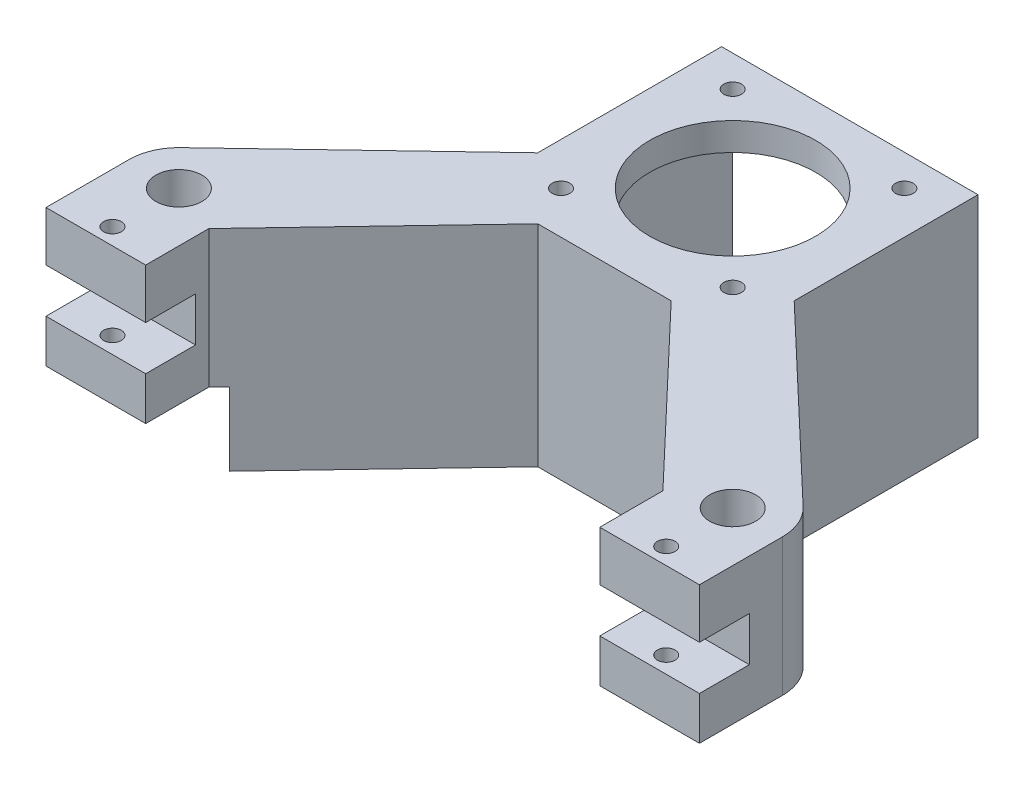
SolidWorks part; units mm, degrees
note: The reader was unsure of these and kept them because the rebuilt part matched: shared geometry of "草图7<7>", "草图7<8>".
ref_plane "前视基准面" through (0, 0, 0) normal (0, 0, 1) x (1, 0, 0)
ref_plane "上视基准面" through (0, 0, 0) normal (0, 1, 0) x (1, 0, 0)
ref_plane "右视基准面" through (0, 0, 0) normal (1, 0, 0) x (0, 0, -1)
sketch "草图6" plane through (0, 0, 0) normal (0, 1, 0) x (1, 0, 0)
  line L1 (-21.15, -21.15) -> (21.15, -21.15)
  line L2 (-21.15, -21.15) -> (-21.15, 21.15)
  line L3 (-21.15, 21.15) -> (21.15, 21.15)
  line L5 (0, 21.15) -> (0, -21.15) construction
  line L6 (-21.15, 0) -> (21.15, 0) construction
  line L8 (21.15, 21.15) -> (21.15, -21.15)
  circle A0 centre (15.5, 15.5) radius 1.6
  circle A1 centre (-15.5, 15.5) radius 1.6
  circle A2 centre (-15.5, -15.5) radius 1.6
  circle A3 centre (15.5, -15.5) radius 1.6
  circle A4 centre (0, 0) radius 15
  point P0 (0, 0)
extrude "凸台-拉伸1" add sketch "草图6" along normal blind 5
sketch "草图7" plane through (0, 5, 0) normal (0, 1, 0) x (1, 0, 0)
  line L1 (54.15, -50) -> (45.85, -50)
  line L2 (21, -10) -> (56.2023, -43.4784)
  line L3 (59, -50) -> (59, -65)
  line L4 (-10, -21) -> (-41, -53.5963)
  line L5 (-21, -10) -> (-56.2023, -43.4784)
  line L6 (10, -21) -> (41, -53.5963)
  line L7 (59, -65) -> (41, -65)
  line L8 (41, -53.5963) -> (41, -65)
  line L9 (-45.85, -50) -> (-54.15, -50)
  line L10 (-41, -53.5963) -> (-41, -65)
  line L11 (-41, -65) -> (-59, -65)
  line L12 (-59, -50) -> (-59, -65)
  arc A0 (-56.2023, -43.4784) -> (-59, -50) centre (-50, -50) ccw
  arc A1 (59, -50) -> (56.2023, -43.4784) centre (50, -50) ccw
  circle A2 centre (-50, -50) radius 4.15
  circle A3 centre (50, -50) radius 4.15
  circle A4 centre (50, -62) radius 1.6
  circle A5 centre (-50, -62) radius 1.6
  dimension "D1" = 18
  dimension "D2" = 18
extrude "凸台-拉伸5" add sketch "草图7" against normal blind 38
extrude "凸台-拉伸7" add sketch "草图7<7>" against normal blind 38 contours A1 A3
sketch "草图7<7>" plane through (0, 5, 0) normal (0, 1, 0) x (1, 0, 0) same geometry as "草图7"
extrude "凸台-拉伸8" add sketch "草图7<8>" against normal blind 38 contours A0 A2
sketch "草图7<8>" plane through (0, 5, 0) normal (0, 1, 0) x (1, 0, 0) same geometry as "草图7"
sketch "草图12" plane through (0, 5, 0) normal (0, 1, 0) x (1, 0, 0)
  line L0 (21.15, 21.15) -> (23.15, 21.15)
  line L1 (21.15, 21.15) -> (21.15, -23.15)
  line L2 (23.15, 21.15) -> (23.15, -23.15)
  line L3 (21.15, -23.15) -> (23.15, -23.15)
extrude "凸台-拉伸11" add sketch "草图12" against normal blind 38
sketch "草图14" plane through (0, 5, 0) normal (0, 1, 0) x (1, 0, 0)
  line L0 (21.15, -23.15) -> (-23.15, -23.15)
  line L1 (21.15, -23.15) -> (21.15, -21.15)
  line L2 (-23.15, -23.15) -> (-23.15, -21.15)
  line L3 (21.15, -21.15) -> (-23.15, -21.15)
extrude "凸台-拉伸12" add sketch "草图14" against normal blind 38
sketch "草图15" plane through (0, 5, 0) normal (0, 1, 0) x (1, 0, 0)
  line L0 (-23.15, -21.15) -> (-23.15, 21.15)
  line L1 (-23.15, -21.15) -> (-21.15, -21.15)
  line L2 (-23.15, 21.15) -> (-21.15, 21.15)
  line L3 (-21.15, -21.15) -> (-21.15, 21.15)
extrude "凸台-拉伸13" add sketch "草图15" against normal blind 38
sketch "草图17" plane through (0, -33, 0) normal (0, -1, 0) x (1, 0, 0)
  line L1 (59.487, 20) -> (39.2, 20)
  line L2 (59.487, 20) -> (59.487, 65)
  line L3 (59.487, 65) -> (39.2, 65)
  line L4 (39.2, 20) -> (39.2, 65)
  line L5 (-39.2, 23.2788) -> (-61.8372, 23.2788)
  line L6 (-39.2, 23.2788) -> (-39.2, 65.4561)
  line L7 (-39.2, 65.4561) -> (-61.8372, 65.4561)
  line L8 (-61.8372, 23.2788) -> (-61.8372, 65.4561)
extrude "切除-拉伸1" cut sketch "草图17" against normal blind 13.2
sketch "草图18" plane through (59, 0, 0) normal (1, 0, 0) x (0, 0, -1)
  line L1 (-65, -4) -> (-56, -4)
  line L2 (-65, -4) -> (-65, -12)
  line L3 (-65, -12) -> (-56, -12)
  line L4 (-56, -4) -> (-56, -12)
extrude "切除-拉伸2" cut sketch "草图18" against normal blind 123
